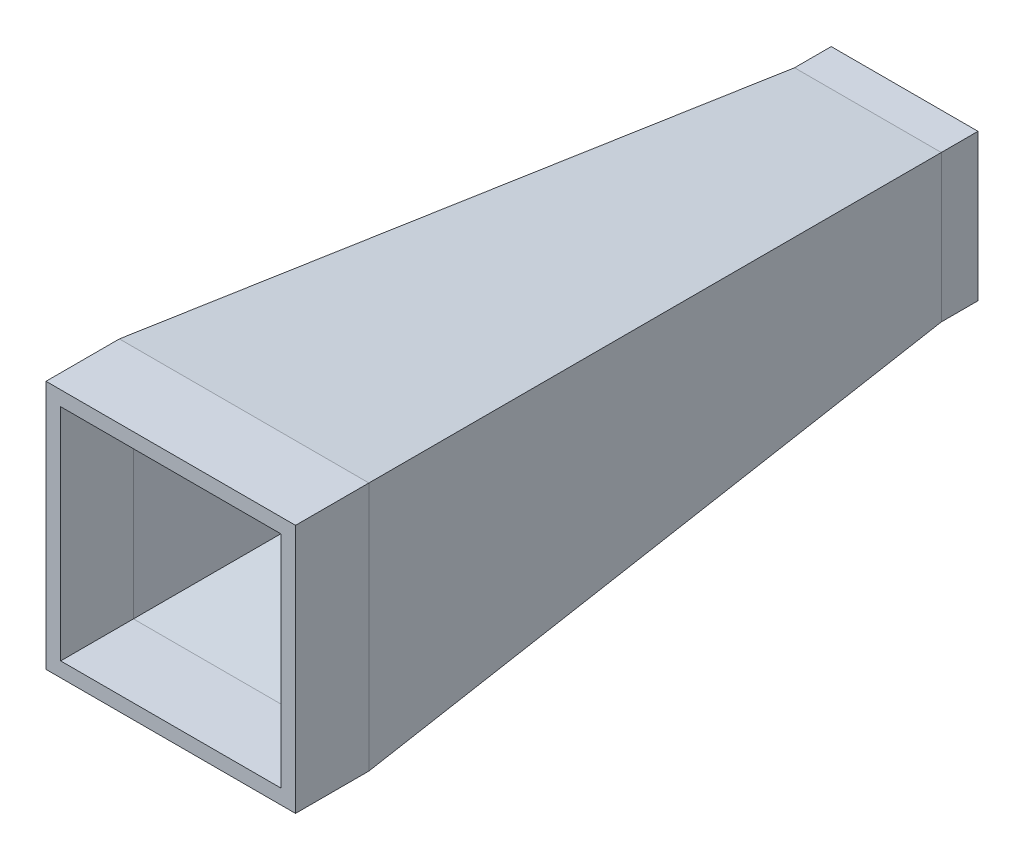
SolidWorks part; units mm, degrees
ref_plane "Front Plane" through (0, 0, 0) normal (0, 0, 1) x (1, 0, 0)
ref_plane "Top Plane" through (0, 0, 0) normal (0, 1, 0) x (1, 0, 0)
ref_plane "Right Plane" through (0, 0, 0) normal (1, 0, 0) x (0, 0, -1)
sketch "Sketch2" plane through (0, 0, 0) normal (0, 0, 1) x (1, 0, 0)
  line L7 (-85, -85) -> (85, -85)
  line L8 (-85, -85) -> (-85, 85)
  line L9 (-85, 85) -> (85, 85)
  line L10 (85, -85) -> (85, 85)
  point P0 (0, 0)
  point P6 (0, 0)
  dimension "D3" = 170
  dimension "D4" = 170
extrude "Boss-Extrude1" add sketch "Sketch2" along normal blind 50
ref_plane "Plane1" through (0, 0, -450) normal (0, 0, -1) x (-1, 0, 0)
sketch "Sketch3" plane through (0, 0, -450) normal (0, 0, -1) x (-1, 0, 0)
  line L7 (-50, -50) -> (50, -50)
  line L8 (-50, -50) -> (-50, 50)
  line L9 (-50, 50) -> (50, 50)
  line L10 (50, -50) -> (50, 50)
  point P0 (0, 0)
  point P6 (0, 0)
  dimension "D1" = 100
  dimension "D2" = 100
extrude "Boss-Extrude2" add sketch "Sketch3" against normal blind 25 separate body
loft "Loft2" add section face at (0, 0, -425) section face at (0, 0, 0) connector at (50, 50, -425) connector at (85, 85, 0)
shell "Shell1" thickness 10 removed face at (0, 0, 50)
